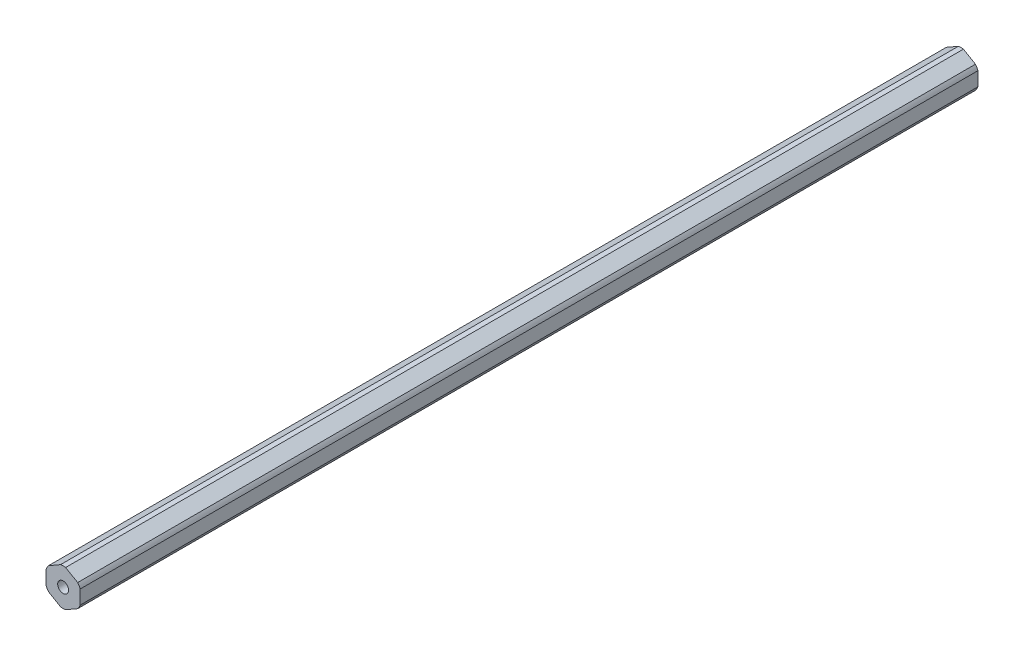
SolidWorks part; units mm, degrees
ref_plane "Front Plane" through (0, 0, 0) normal (0, 0, 1) x (1, 0, 0)
ref_plane "Top Plane" through (0, 0, 0) normal (0, 1, 0) x (1, 0, 0)
ref_plane "Right Plane" through (0, 0, 0) normal (1, 0, 0) x (0, 0, -1)
sketch "Sketch1" plane through (0, 0, 0) normal (0, 0, 1) x (1, 0, 0)
  line L1 (0, 7.3323) -> (-6.35, 3.6662)
  line L2 (-6.35, 3.6662) -> (-6.35, -3.6662)
  line L3 (-6.35, -3.6662) -> (0, -7.3323)
  line L4 (0, -7.3323) -> (6.35, -3.6662)
  line L5 (6.35, -3.6662) -> (6.35, 3.6662)
  line L6 (6.35, 3.6662) -> (0, 7.3323)
  circle A0 centre (0, 0) radius 6.35 construction
  circle A1 centre (0, 0) radius 6.858
  dimension "D1" = 12.7
  dimension "D2" = 13.716
extrude "Boss-Extrude1" add sketch "Sketch1" along normal mid plane 333.375 contours L5 A1 L6 L1 L2 L3 L4 region at (0, 0, 0)
hole_wizard "#10-32 Tapped Hole1" positions "3DSketch1" profile "Sketch2" tap size "#10-32" standard "ANSI Inch"
sketch3d "3DSketch1"
  line L0 (0, 0, 166.6875) -> (0, 0, -166.6875) construction
  line L1 (0, 0, 166.6875) -> (0, 0, -166.6875) construction
  point P0 (0, 0, 166.6875)
  point P4 (0, 0, -166.6875)
sketch "Sketch2" plane through (0, 0, 166.6875) normal (1, 0, 0) x (0, -1, 0)
  line L0 (0, 0) -> (0, 17.5608)
  line L1 (0, 17.5608) -> (2.0193, 16.3474)
  line L2 (2.0193, 16.3474) -> (2.0193, 0)
  line L5 (2.0193, 0) -> (0, 0)
  line L10 (0, 17.5608) -> (-2.0193, 16.3474) construction
  line L11 (0, -6.35) -> (0, 107.95) construction
  dimension "Tap Drill Dia." = 4.0386
  dimension "Tap Drill Depth" = 16.3474
  dimension "Drill Angle" = 118
cosmetic thread "Hole Thread1" parameters "D1"=13.97, "D2"=4.826
cosmetic thread "Hole Thread2" parameters "D1"=13.97, "D2"=4.826
